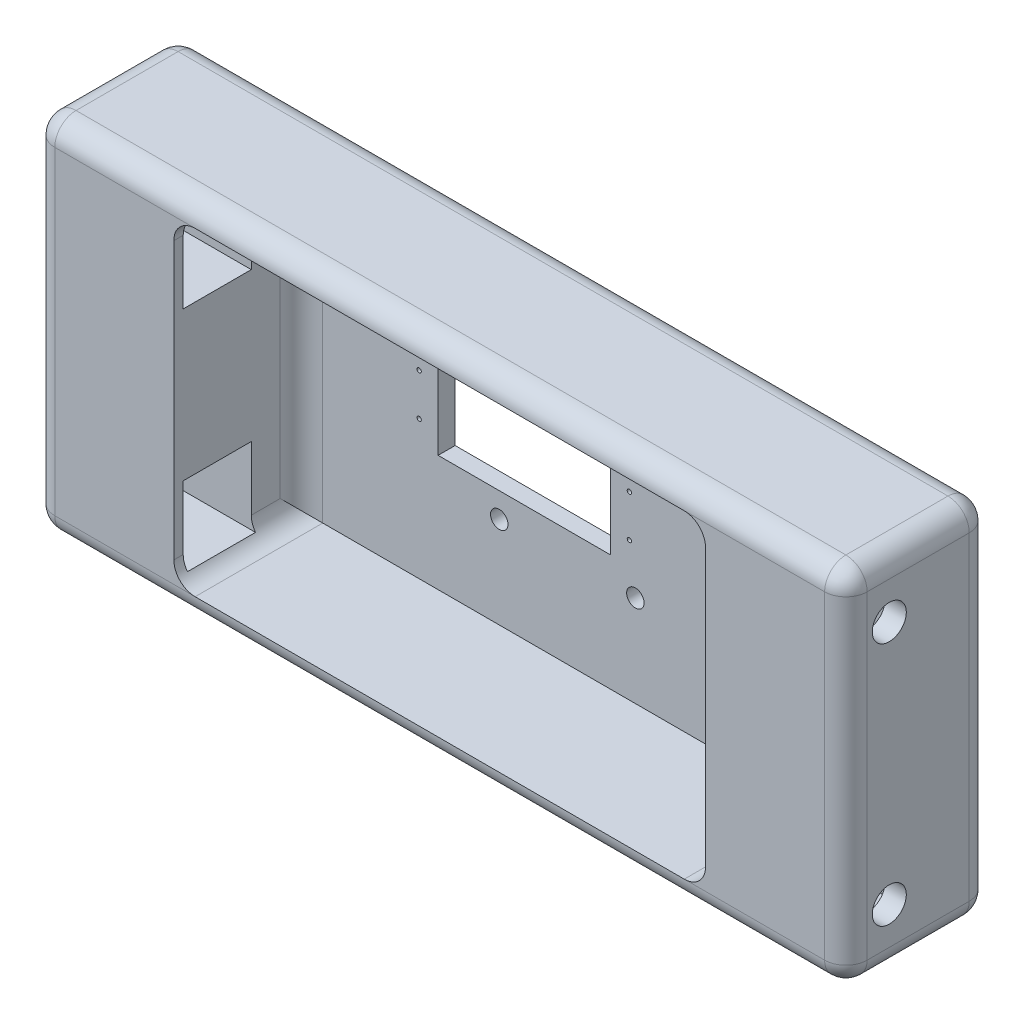
SolidWorks part; units mm, degrees
ref_plane "Plano frontal" through (0, 0, 0) normal (0, 0, 1) x (1, 0, 0)
ref_plane "Plano superior" through (0, 0, 0) normal (0, 1, 0) x (1, 0, 0)
ref_plane "Plano direito" through (0, 0, 0) normal (1, 0, 0) x (0, 0, -1)
sketch "Esboço1" plane through (0, 0, 0) normal (0, 0, 1) x (1, 0, 0)
  line L1 (-62.5, -37.5) -> (62.5, -37.5)
  line L2 (-62.5, -37.5) -> (-62.5, 37.5)
  line L3 (-62.5, 37.5) -> (62.5, 37.5)
  line L4 (62.5, -37.5) -> (62.5, 37.5)
  line L5 (-62.5, -37.5) -> (62.5, 37.5) construction
  line L6 (-62.5, 37.5) -> (62.5, -37.5) construction
  line L7 (-95.5, -42.5) -> (95.5, -42.5)
  line L8 (-95.5, -42.5) -> (-95.5, 42.5)
  line L9 (-95.5, 42.5) -> (95.5, 42.5)
  line L10 (95.5, -42.5) -> (95.5, 42.5)
  line L11 (-95.5, -42.5) -> (95.5, 42.5) construction
  line L12 (-95.5, 42.5) -> (95.5, -42.5) construction
  point P0 (0, 0)
  point P6 (0, 0)
  dimension "D1" = 125
  dimension "D2" = 75
  dimension "D3" = 33
  dimension "D4" = 5
extrude "Ressalto-extrusão1" add sketch "Esboço1" along normal mid plane 30
sketch "Esboço2" plane through (-95.5, 0, 0) normal (-1, 0, 0) x (0, 0, 1)
  line L0 (15, -42.5) -> (-15, -42.5) construction
  line L7 (15, 42.5) -> (15, -42.5) construction
  circle A0 centre (4.8, -28.75) radius 4
  point P0 (4.8, -28.75)
  dimension "D3" = 8
  dimension "D1" = 13.75
  dimension "D2" = 10.2
extrude "Corte-extrusão1" cut sketch "Esboço2" against normal up to surface (191 mm away) contours A0 up to face at (95.5, 0, 0)
sketch "Esboço3" plane through (-62.5, 0, 0) normal (1, 0, 0) x (0, 0, -1)
  line L5 (-12.8, -35.5) -> (3.2, -35.5)
  line L6 (-12.8, -35.5) -> (-12.8, -17.5)
  line L7 (-12.8, -17.5) -> (3.2, -17.5)
  line L8 (3.2, -35.5) -> (3.2, -17.5)
  line L9 (15, 37.5) -> (15, -37.5) construction
  line L11 (-15, -37.5) -> (15, -37.5) construction
  dimension "D1" = 11.8
  dimension "D2" = 2
  dimension "D3" = 18
  dimension "D4" = 16
extrude "Corte-extrusão2" cut sketch "Esboço3" against normal blind 28
mirror "Espelhar1" about plane through (0, 0, 0) normal (0, 1, 0) of "Corte-extrusão1"
mirror "Espelhar2" about plane through (0, 0, 0) normal (0, 1, 0) of "Corte-extrusão2"
mirror "Espelhar3" about plane through (0, 0, 0) normal (1, 0, 0) of "Espelhar2"
sketch "Esboço4" plane through (0, 0, -15) normal (0, 0, -1) x (-1, 0, 0)
  line L0 (-10.13, 10.15) -> (30.37, -10.15) construction
  line L1 (-95.5, 42.5) -> (95.5, 42.5)
  line L2 (-95.5, 42.5) -> (-95.5, -42.5)
  line L3 (-95.5, -42.5) -> (95.5, -42.5)
  line L4 (95.5, 42.5) -> (95.5, -42.5)
  line L5 (-10.13, -10.15) -> (30.37, -10.15)
  line L6 (-10.13, -10.15) -> (-10.13, 10.15)
  line L7 (-10.13, 10.15) -> (30.37, 10.15)
  line L8 (30.37, -10.15) -> (30.37, 10.15)
  line L9 (-10.13, -10.15) -> (30.37, 10.15) construction
  line L11 (-14.59, 4.925) -> (34.83, 4.925) construction
  line L12 (-14.59, 4.925) -> (-14.59, -4.925) construction
  line L13 (-14.59, -4.925) -> (34.83, -4.925) construction
  line L14 (34.83, 4.925) -> (34.83, -4.925) construction
  line L15 (-14.59, 4.925) -> (34.83, -4.925) construction
  line L16 (-14.59, -4.925) -> (34.83, 4.925) construction
  circle A0 centre (-14.59, -4.925) radius 0.5
  circle A1 centre (34.83, -4.925) radius 0.5
  circle A2 centre (34.83, 4.925) radius 0.5
  circle A3 centre (-14.59, 4.925) radius 0.5
  point P10 (10.12, 0)
  dimension "D5" = 1
  dimension "D1" = 20.3
  dimension "D2" = 40.5
  dimension "D3" = 65.13
  dimension "D4" = 32.35
  dimension "D6" = 9.85
  dimension "D7" = 49.42
extrude "Ressalto-extrusão5" add sketch "Esboço4" along normal blind 4
fillet "Filete1" radius 5 19 edges at (95.5, 0, 15) (-95.5, 0, 15) (95.5, 0, -19) (0, -42.5, -19) (0, 42.5, -19) (-95.5, 0, -19) (-95.5, -42.5, -2) (-95.5, 42.5, -2) (95.5, -42.5, -2) (95.5, 42.5, -2) (0, -42.5, 15) (0, 42.5, 15) (62.5, 37.5, 0) (-62.5, 37.5, 0) (0, 37.5, -15) (-62.5, 0, -15) (62.5, 0, -15) (62.5, -37.5, 0) (-62.5, -37.5, 0)
sketch "Esboço5" plane through (0, 0, -19) normal (0, 0, -1) x (-1, 0, 0)
  line L1 (16, -16) -> (-16, -16) construction
  line L2 (16, -16) -> (16, 16) construction
  line L3 (16, 16) -> (-16, 16) construction
  line L4 (-16, -16) -> (-16, 16) construction
  line L5 (16, -16) -> (-16, 16) construction
  line L6 (16, 16) -> (-16, -16) construction
  circle A0 centre (-16, 16) radius 2.05
  circle A1 centre (16, 16) radius 2.05
  circle A2 centre (16, -16) radius 2.05
  circle A3 centre (-16, -16) radius 2.05
  point P0 (0, 0)
  dimension "D1" = 4.1
  dimension "D2" = 32
extrude "Corte-extrusão3" cut sketch "Esboço5" against normal up to surface (4 mm away) up to face at (14.09, 4.925, -15)
